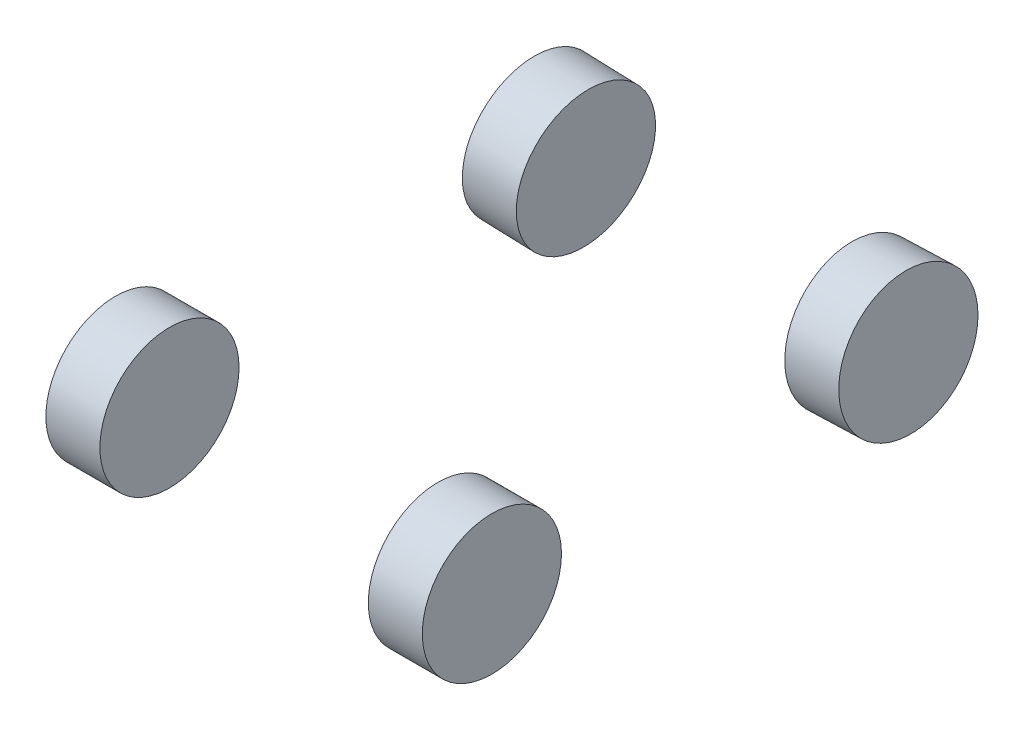
SolidWorks part; units mm, degrees
ref_plane "Front Plane" through (0, 0, 0) normal (0, 0, 1) x (1, 0, 0)
ref_plane "Top Plane" through (0, 0, 0) normal (0, 1, 0) x (1, 0, 0)
ref_plane "Right Plane" through (0, 0, 0) normal (1, 0, 0) x (0, 0, -1)
sketch3d "3DSketch1"
  line L0 (-519.3255, 235, 2080) -> (-681.2452, 235, 2080) construction
  line L1 (-681.2452, 235, 2080) -> (-684.2452, 235, 2080) construction
  line L2 (-519.3255, 235, 2080) -> (-412.1048, 235, 2080) construction
  line L3 (-600, 235, 2080) -> (-600, 486.5176, 2141.8052) construction
  line L4 (-600, 235, 2080) -> (-600, 173.1948, 2331.5176) construction
  line L5 (-600, 235, 2080) -> (-600, 235, 2339) construction
  arc A0 (-681.2452, 468.1652, 2050.6914) -> (-681.2452, 1.8348, 2109.3086) centre (-681.2452, 235, 2080) ccw construction
  arc A1 (-681.2452, 468.1652, 2050.6914) -> (-681.2452, 1.8348, 2109.3086) centre (-681.2452, 235, 2080) ccw construction
  arc A2 (-519.3255, 468.1652, 2050.6914) -> (-519.3255, 1.8348, 2109.3086) centre (-519.3255, 235, 2080) ccw construction
  arc A3 (-519.3255, 468.1652, 2050.6914) -> (-519.3255, 1.8348, 2109.3086) centre (-519.3255, 235, 2080) ccw construction
  arc A4 (-681.2452, 1.8348, 2109.3086) -> (-681.2452, 468.1652, 2050.6914) centre (-681.2452, 235, 2080) ccw construction
  arc A5 (-681.2452, 1.8348, 2109.3086) -> (-681.2452, 468.1652, 2050.6914) centre (-681.2452, 235, 2080) ccw construction
  arc A6 (-519.3255, 1.8348, 2109.3086) -> (-519.3255, 468.1652, 2050.6914) centre (-519.3255, 235, 2080) ccw construction
  arc A7 (-519.3255, 1.8348, 2109.3086) -> (-519.3255, 468.1652, 2050.6914) centre (-519.3255, 235, 2080) ccw construction
  circle A10 centre (-600, 235, 2080) radius 259
  point P3 (-916.2452, 235, 2080)
  point P4 (-916.2452, 235, 2080)
  point P8 (-754.3255, 235, 2080)
  point P9 (-754.3255, 235, 2080)
  point P13 (-916.2452, 235, 2080)
  point P14 (-916.2452, 235, 2080)
  point P16 (-754.3255, 235, 2080)
  point P17 (-754.3255, 235, 2080)
  point P22 (-341, 235, 2080)
  dimension "D2" = 518
  dimension "D1" = 3
sketch3d "3DSketch2"
  line L0 (-519.1248, 232.1758, 530) -> (-680.9459, 237.8267, 530) construction
  line L1 (-600.0354, 235.0012, 530) -> (-600.0354, 235.0012, 789) construction
  arc A0 (-672.8078, 470.8721, 500.8691) -> (-689.084, 4.7813, 559.1309) centre (-680.9459, 237.8267, 530) ccw construction
  arc A1 (-689.084, 4.7813, 559.1309) -> (-672.8078, 470.8721, 500.8691) centre (-680.9459, 237.8267, 530) ccw construction
  arc A2 (-527.2629, -0.8696, 559.1309) -> (-510.9867, 465.2212, 500.8691) centre (-519.1248, 232.1758, 530) ccw construction
  arc A3 (-510.9867, 465.2212, 500.8691) -> (-527.2629, -0.8696, 559.1309) centre (-519.1248, 232.1758, 530) ccw construction
  arc A4 (-672.8078, 470.8721, 500.8691) -> (-689.084, 4.7813, 559.1309) centre (-680.9459, 237.8267, 530) ccw construction
  arc A5 (-689.084, 4.7813, 559.1309) -> (-672.8078, 470.8721, 500.8691) centre (-680.9459, 237.8267, 530) ccw construction
  arc A6 (-527.2629, -0.8696, 559.1309) -> (-510.9867, 465.2212, 500.8691) centre (-519.1248, 232.1758, 530) ccw construction
  arc A7 (-510.9867, 465.2212, 500.8691) -> (-527.2629, -0.8696, 559.1309) centre (-519.1248, 232.1758, 530) ccw construction
  circle A10 centre (-600.0354, 235.0012, 530) radius 259
  point P3 (-915.8027, 246.0281, 530)
  point P5 (-915.8027, 246.0281, 530)
  point P6 (-915.8027, 246.0281, 530)
  point P7 (-915.8027, 246.0281, 530)
  point P11 (-753.9817, 240.3772, 530)
  point P13 (-753.9817, 240.3772, 530)
  point P14 (-753.9817, 240.3772, 530)
  point P15 (-753.9817, 240.3772, 530)
  point P16 (-599.7502, 234.9913, 530)
  point P19 (-341.1931, 225.9623, 530)
  point P20 (-600.0354, 235.0012, 789)
  dimension "D1" = 518
ref_plane "Plane1" through (-526.5904, 18.3889, 0) normal (-0.9994, 0.0349, 0) x (0, 0, 1)
extrude "Boss-Extrude2" add sketch "3DSketch2" along direction (-0.9994, 0.0349, 0) on the side of the normal blind 100.5 and the other way blind 100.5 separate body
ref_plane "Plane2" through (-519.3255, 0, 0) normal (-1, 0, 0) x (0, 0, 1)
extrude "Boss-Extrude3" add sketch "3DSketch1" along direction (-1, 0, 0) on the side of the normal blind 100.5 and the other way blind 100.5 separate body
mirror "Mirror1" about plane through (0, 0, 0) normal (1, 0, 0) of bodies 102 103
